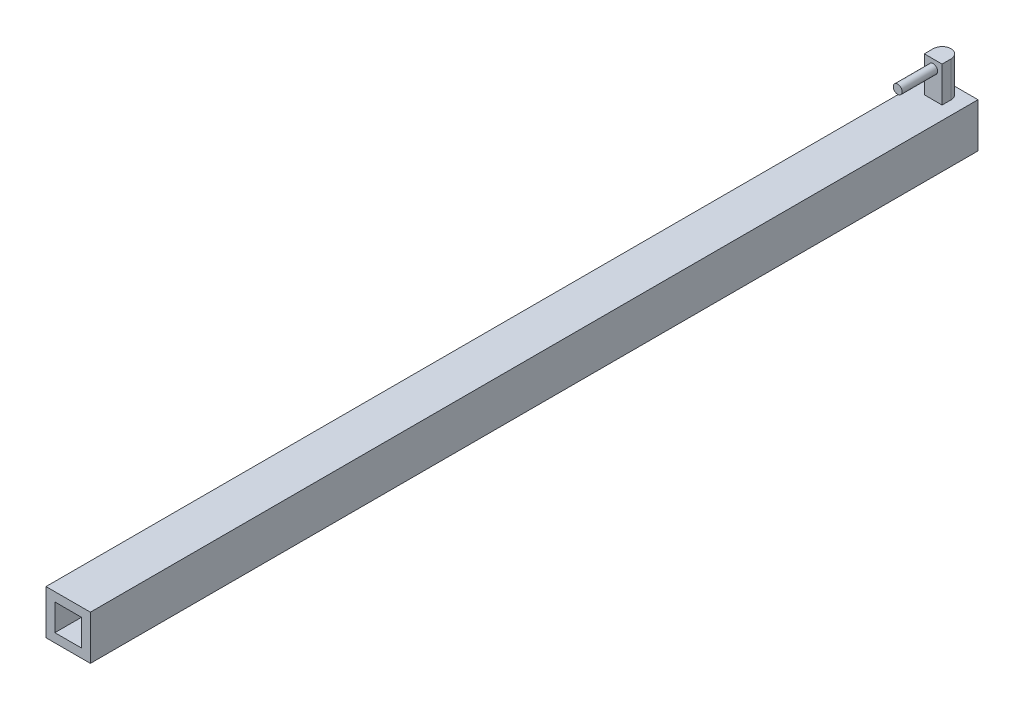
SolidWorks part; units mm, degrees
material "6061 Alloy"
ref_plane "Front Plane" through (0, 0, 0) normal (0, 0, 1) x (1, 0, 0)
ref_plane "Top Plane" through (0, 0, 0) normal (0, 1, 0) x (1, 0, 0)
ref_plane "Right Plane" through (0, 0, 0) normal (1, 0, 0) x (0, 0, -1)
sketch "Sketch1" plane through (0, 0, 0) normal (0, 0, 1) x (1, 0, 0)
  line L0 (-12.5, 12.5) -> (12.5, 12.5)
  line L1 (-7.5, -7.5) -> (7.5, -7.5)
  line L2 (-7.5, -7.5) -> (-7.5, 7.5)
  line L3 (-7.5, 7.5) -> (7.5, 7.5)
  line L4 (7.5, -7.5) -> (7.5, 7.5)
  line L5 (-7.5, -7.5) -> (7.5, 7.5) construction
  line L6 (-7.5, 7.5) -> (7.5, -7.5) construction
  line L7 (12.5, -12.5) -> (12.5, 12.5)
  line L8 (-12.5, -12.5) -> (12.5, -12.5)
  line L9 (-12.5, -12.5) -> (-12.5, 12.5)
  point P0 (0, 0)
  dimension "D1" = 15
  dimension "D2" = 15
  dimension "D3" = 5
extrude "Boss-Extrude1" add sketch "Sketch1" along normal blind 500
sketch "Sketch2" plane through (0, 12.5, 0) normal (0, 1, 0) x (1, 0, 0)
  line L0 (0, 0) -> (0, -49.9364) construction
  line L2 (-5, -12.7312) -> (5, -12.7312)
  line L3 (-5, -12.7312) -> (-5, -2.7312)
  line L4 (-5, -2.7312) -> (5, -2.7312)
  line L5 (5, -12.7312) -> (5, -2.7312)
  line L6 (-5, -12.7312) -> (5, -2.7312) construction
  line L7 (-5, -2.7312) -> (5, -12.7312) construction
  point P3 (0, -7.7312)
  dimension "D1" = 10
  dimension "D2" = 10
extrude "Boss-Extrude2" add sketch "Sketch2" along normal blind 20
sketch "Sketch3" plane through (0, 0, 12.7312) normal (0, 0, 1) x (1, 0, 0)
  line L0 (0, 32.5) -> (0, 12.5) construction
  line L1 (-5, 32.5) -> (5, 32.5) construction
  line L2 (-5, 12.5) -> (5, 12.5) construction
  circle A0 centre (0, 27.7071) radius 2.5
extrude "Boss-Extrude3" add sketch "Sketch3" along normal blind 20
fillet "Fillet2" radius 5 1 edges at (5, 22.5, 2.7312)
fillet "Fillet3" radius 5 1 edges at (-5, 22.5, 2.7312)
sketch "Sketch4" plane through (0, -12.5, 0) normal (0, -1, 0) x (1, 0, 0)
  line L0 (0, 0) -> (0, 177.3433) construction
  line L1 (-12.5, 0) -> (12.5, 0) construction
  circle A0 centre (0, 70.9867) radius 4.5
  dimension "D1" = 9
extrude "Cut-Extrude1" cut sketch "Sketch4" against normal blind 5
